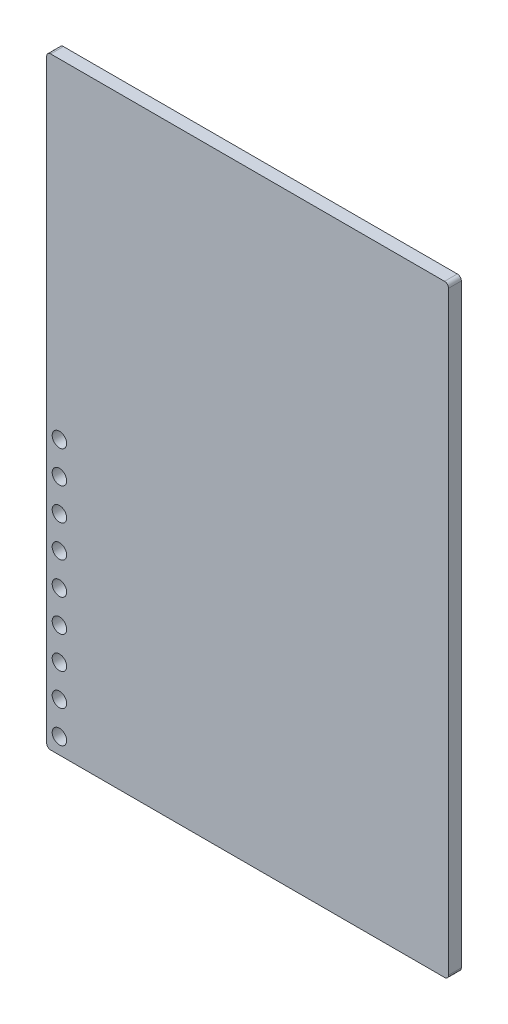
SolidWorks part; units mm, degrees
ref_plane "Front Plane" through (0, 0, 0) normal (0, 0, 1) x (1, 0, 0)
ref_plane "Top Plane" through (0, 0, 0) normal (0, 1, 0) x (1, 0, 0)
ref_plane "Right Plane" through (0, 0, 0) normal (1, 0, 0) x (0, 0, -1)
sketch "Sketch1" plane through (0, 0, 0) normal (0, 1, 0) x (1, 0, 0)
  line L1 (0, 0) -> (100, 0)
  line L2 (0, 0) -> (0, 3.175)
  line L3 (0, 3.175) -> (100, 3.175)
  line L4 (100, 0) -> (100, 3.175)
  dimension "D1" = 100
  dimension "D2" = 3.175
extrude "Boss-Extrude1" add sketch "Sketch1" along normal blind 150
sketch "Sketch2" plane through (0, 0, 0) normal (0, 0, 1) x (1, 0, 0)
  line L0 (6.35, 8) -> (0, 8) construction
  line L5 (0, 0) -> (6.35, 0)
  line L6 (0, 0) -> (0, 16)
  line L8 (6.35, 0) -> (6.35, 16) construction
  line L9 (6.35, 16) -> (0, 16) construction
  line L10 (6.35, 16) -> (6.35, 24) construction
  line L11 (6.35, 24) -> (0, 24) construction
  line L12 (0, 150) -> (0, 0) construction
  line L13 (0, 24) -> (0, 48)
  line L14 (0, 150) -> (0, 0) construction
  line L15 (0, 48) -> (11.1036, 48)
  line L16 (0, 24) -> (0, 32)
  line L17 (0, 32) -> (0, 40)
  line L18 (0, 40) -> (0, 48)
  circle A4 centre (3.175, 4) radius 1.8
  circle A5 centre (3.175, 12) radius 1.8
  circle A6 centre (3.175, 20) radius 1.8
  circle A7 centre (3.175, 44) radius 1.8
  circle A8 centre (3.175, 36) radius 1.8
  circle A9 centre (3.175, 28) radius 1.8
  circle A10 centre (3.175, 68) radius 1.8
  circle A11 centre (3.175, 60) radius 1.8
  circle A12 centre (3.175, 52) radius 1.8
  dimension "D5" = 24
  dimension "D6" = 4
  dimension "D7" = 8
  dimension "D3" = 8
  dimension "D4" = 3.6
  dimension "D1" = 6.35
  dimension "D2" = 8
  dimension "D8" = 3.175
  dimension "D9" = 8
extrude "Cut-Extrude2" cut sketch "Sketch2" against normal blind 5 contours A10
extrude "Cut-Extrude3" cut sketch "Sketch2<14>" against normal blind 5 contours A11
sketch "Sketch2<14>" plane through (0, 0, 0) normal (0, 0, 1) x (1, 0, 0) same geometry as "Sketch2"
extrude "Cut-Extrude4" cut sketch "Sketch2<15>" against normal blind 5 contours A12
sketch "Sketch2<15>" plane through (0, 0, 0) normal (0, 0, 1) x (1, 0, 0) same geometry as "Sketch2"
extrude "Cut-Extrude5" cut sketch "Sketch2<16>" against normal blind 5 contours A7
sketch "Sketch2<16>" plane through (0, 0, 0) normal (0, 0, 1) x (1, 0, 0) same geometry as "Sketch2"
extrude "Cut-Extrude6" cut sketch "Sketch2<17>" against normal blind 5 contours A8
sketch "Sketch2<17>" plane through (0, 0, 0) normal (0, 0, 1) x (1, 0, 0) same geometry as "Sketch2"
extrude "Cut-Extrude7" cut sketch "Sketch2<18>" against normal blind 5 contours A9
sketch "Sketch2<18>" plane through (0, 0, 0) normal (0, 0, 1) x (1, 0, 0) same geometry as "Sketch2"
extrude "Cut-Extrude8" cut sketch "Sketch2<19>" against normal blind 5 contours A6
sketch "Sketch2<19>" plane through (0, 0, 0) normal (0, 0, 1) x (1, 0, 0) same geometry as "Sketch2"
extrude "Cut-Extrude9" cut sketch "Sketch2<20>" against normal blind 5 contours A5
sketch "Sketch2<20>" plane through (0, 0, 0) normal (0, 0, 1) x (1, 0, 0) same geometry as "Sketch2"
extrude "Cut-Extrude10" cut sketch "Sketch2<21>" against normal blind 5 contours A4
sketch "Sketch2<21>" plane through (0, 0, 0) normal (0, 0, 1) x (1, 0, 0) same geometry as "Sketch2"
fillet "Fillet1" radius 1 4 edges at (0, 0, -1.5875) (0, 150, -1.5875) (100, 150, -1.5875) (100, 0, -1.5875)
